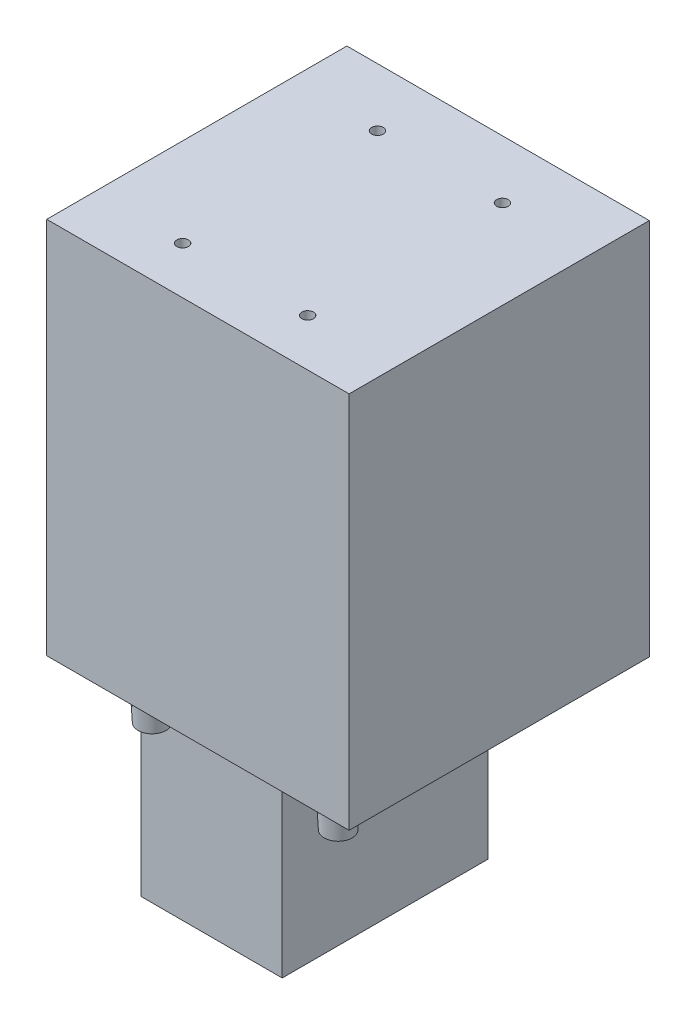
SolidWorks part; units mm, degrees
ref_plane "Front Plane" through (0, 0, 0) normal (0, 0, 1) x (1, 0, 0)
ref_plane "Top Plane" through (0, 0, 0) normal (0, 1, 0) x (1, 0, 0)
ref_plane "Right Plane" through (0, 0, 0) normal (1, 0, 0) x (0, 0, -1)
sketch "Sketch1" plane through (0, 0, 0) normal (0, 1, 0) x (1, 0, 0)
  line L0 (-40.5, -8.125) -> (11.5, -8.125) construction
  line L1 (0, 0) -> (-16.25, 0)
  line L2 (0, 0) -> (0, 52)
  line L3 (0, 52) -> (-16.25, 52)
  line L4 (-16.25, 0) -> (-16.25, 52)
  line L5 (-40.5, 0) -> (11.5, 0)
  line L6 (-40.5, 0) -> (-40.5, -16.25)
  line L7 (-40.5, -16.25) -> (11.5, -16.25)
  line L8 (11.5, 0) -> (11.5, -16.25)
  line L9 (-33.375, 0) -> (-33.375, -16.25) construction
  line L10 (4.375, 0) -> (4.375, -16.25) construction
  line L11 (-14.5, 25.375) -> (-14.5, -8.125) construction
  line L12 (-25.25, 25.375) -> (-3.75, 25.375) construction
  line L13 (-25.25, 25.375) -> (-25.25, -8.125) construction
  line L14 (-25.25, -8.125) -> (-3.75, -8.125) construction
  line L15 (-3.75, 25.375) -> (-3.75, -8.125) construction
  line L16 (-40.5, -16.25) -> (11.5, -16.25)
  line L17 (-40.5, -16.25) -> (-40.5, 35.375)
  line L18 (-40.5, 35.375) -> (11.5, 35.375)
  line L19 (11.5, -16.25) -> (11.5, 35.375)
  circle A0 centre (-30.5, -8.125) radius 2.875
  circle A1 centre (1.5, -8.125) radius 2.875
  circle A2 centre (-25.25, 25.375) radius 1
  circle A3 centre (-3.75, 25.375) radius 1
  circle A4 centre (-3.75, -8.125) radius 1
  circle A5 centre (-25.25, -8.125) radius 1
  point P29 (-11.8266, 25.375)
  point P30 (-14.5, -8.125)
  dimension "D1" = 32
  dimension "D2" = 5.75
  dimension "D9" = 2
  dimension "D3" = 16.25
  dimension "D4" = 1.5
  dimension "D5" = 10
  dimension "D6" = 10
  dimension "D7" = 21.5
  dimension "D8" = 33.5
  dimension "D10" = 10
extrude "Boss-Extrude1" add sketch "Sketch1" along normal blind 65 contours L18 L17 L5 L4 A2 | L18 L4 L1 L2 A3 | L5 L19 L18 L2 | L8 L5 L1 L6 L7 A5 A4 A1 A0 | A0 | A1 | A4 | A3 | A2 | A5 region at (-14.5, 0, 8.125) region at (-8.149, 0, -17.6453) region at (5.75, 0, -17.6875) region at (-28.3865, 0, -17.6592) region at (-30.5, 0, 8.125) region at (1.5, 0, 8.125) region at (-25.25, 0, -25.375) region at (-3.75, 0, -25.375) region at (-3.75, 0, 8.125) region at (-25.25, 0, 8.125)
extrude "Cut-Extrude1" cut sketch "Sketch1<3>" against normal blind 15 from surface contours A4 | A5 | A3 | A2 region at (-25.25, 0, -25.375) region at (-3.75, 0, -25.375) region at (-3.75, 0, 8.125) region at (-25.25, 0, 8.125) starting at face at (-14.5, 65, -9.5625)
sketch "Sketch1<3>" plane through (0, 0, 0) normal (0, 1, 0) x (1, 0, 0) same geometry as "Sketch1"
extrude "Boss-Extrude2" add sketch "Sketch1<4>" against normal blind 44 contours L18 L17 L5 L4 A2 | A2 region at (-28.3865, 0, -17.6592) region at (-25.25, 0, -25.375)
sketch "Sketch1<4>" plane through (0, 0, 0) normal (0, 1, 0) x (1, 0, 0) same geometry as "Sketch1"
extrude "Boss-Extrude3" add sketch "Sketch1<5>" against normal blind 9 draft 3 contours A1 | A0 region at (-30.5, 0, 8.125) region at (1.5, 0, 8.125)
sketch "Sketch1<5>" plane through (0, 0, 0) normal (0, 1, 0) x (1, 0, 0) same geometry as "Sketch1"
